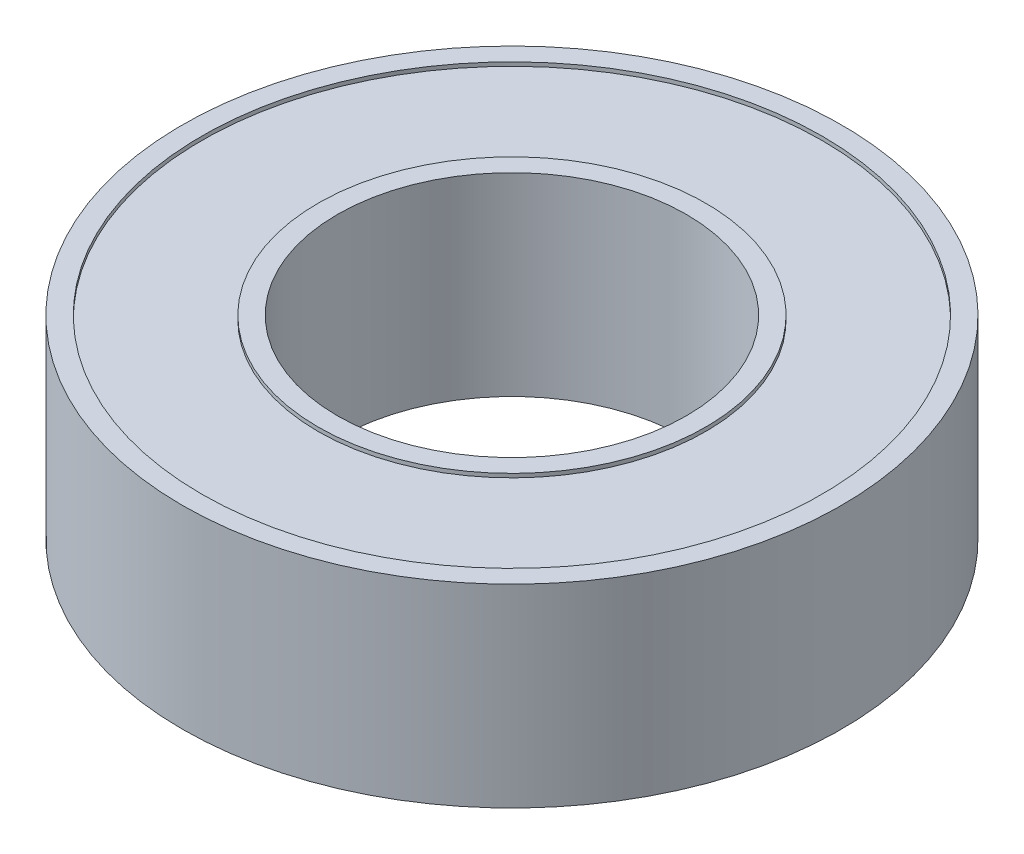
SolidWorks part; units mm, degrees
material "1060-H16"
ref_plane "Front Plane" through (0, 0, 0) normal (0, 0, 1) x (1, 0, 0)
ref_plane "Top Plane" through (0, 0, 0) normal (0, 1, 0) x (1, 0, 0)
ref_plane "Right Plane" through (0, 0, 0) normal (1, 0, 0) x (0, 0, -1)
sketch "Sketch1" plane through (0, 0, 0) normal (0, 1, 0) x (1, 0, 0)
  circle A0 centre (0, 0) radius 4.5
  circle A1 centre (0, 0) radius 8.5
  dimension "D1" = 9
  dimension "D2" = 17
extrude "Boss-Extrude1" add sketch "Sketch1" along normal mid plane 5
sketch "Sketch2" plane through (0, 2.5, 0) normal (0, 1, 0) x (1, 0, 0)
  circle A0 centre (0, 0) radius 4.5 construction
  circle A1 centre (0, 0) radius 8.5
  circle A2 centre (0, 0) radius 8.5
  circle A3 centre (0, 0) radius 4.5
  circle A5 centre (0, 0) radius 5
  circle A8 centre (0, 0) radius 8
  dimension "D1" = 0
  dimension "D2" = 0.5
  dimension "D3" = 0.5
extrude "Cut-Extrude1" cut sketch "Sketch2" against normal blind 0.1 contours A8 A5 region at (-7.7737, 2.5, 0)
mirror "Mirror1" about plane through (0, 0, 0) normal (0, 1, 0) of "Cut-Extrude1"
